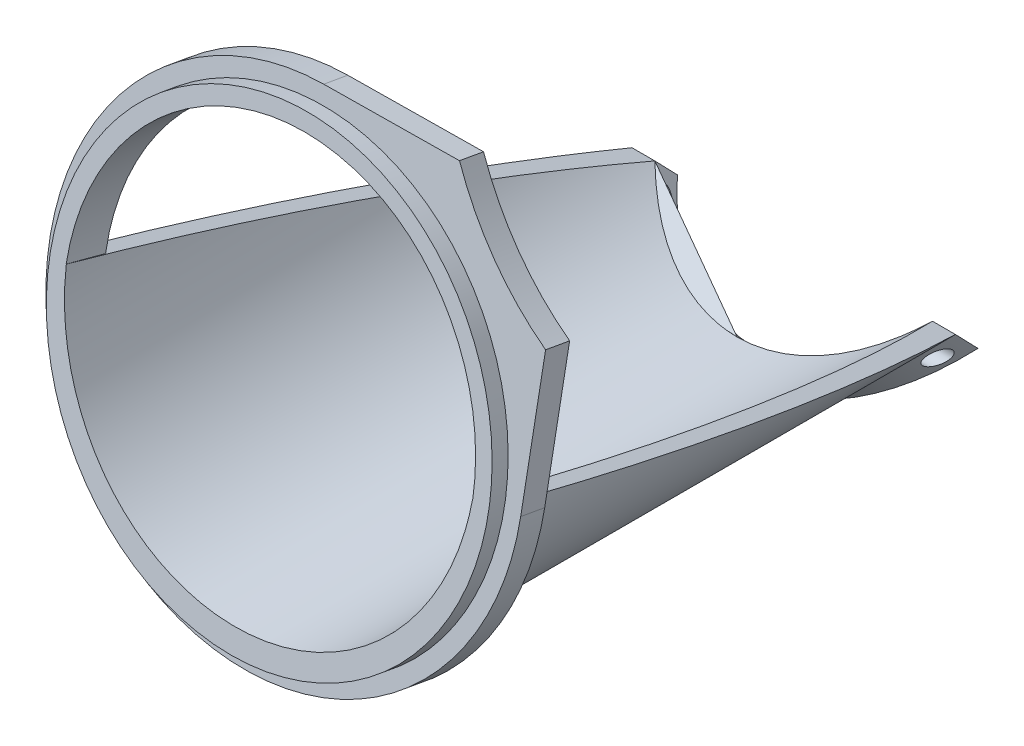
SolidWorks part; units mm, degrees
ref_plane "Front Plane" through (0, 0, 0) normal (0, 0, 1) x (1, 0, 0)
ref_plane "Top Plane" through (0, 0, 0) normal (0, 1, 0) x (1, 0, 0)
ref_plane "Right Plane" through (0, 0, 0) normal (1, 0, 0) x (0, 0, -1)
ref_plane "Plane1" through (0, 0, 90) normal (0, 0, 1) x (1, 0, 0)
ref_axis "Axis1" through (-88.99, 0, 90) along (1, 0, 0)
ref_plane "Plane2" through (0, 15.3909, 87.2862) normal (0, 0.1736, 0.9848) x (1, 0, 0)
sketch "Sketch1" plane through (0, 0, 0) normal (0, 0, 1) x (1, 0, 0)
  line L1 (25, 27) -> (25, 29)
  line L2 (-26.9258, 29) -> (-25, 29)
  line L5 (-25, 29) -> (-25, 27)
  line L6 (25, 29) -> (26.9258, 29)
  arc A0 (25, 27) -> (-25, 27) centre (0, 27) cw
  arc A1 (26.9258, 29) -> (-26.9258, 29) centre (0, 27) cw
  point P1 (0, 0)
  point P6 (0, 0)
  dimension "D1" = 25
  dimension "D3" = 27
  dimension "D2" = 50
  dimension "D4" = 2
extrude "Main" add sketch "Sketch1" along normal blind 90
sketch "Sketch11" plane through (0, 0, 0) normal (1, 0, 0) x (0, 0, -1)
  line L0 (-84.8865, 29) -> (0, 29)
  line L1 (-84.8865, 29) -> (-85.4155, 26)
  line L3 (0, 3.113) -> (0, 29)
  line L6 (0, 27) -> (0, 2) construction
  line L7 (-85.4155, 26) -> (0, 3.113)
  line L8 (-70.2879, 111.7928) -> (-104.2844, -81.0109) construction
  line L9 (-90, 29) -> (0, 29) construction
  point P4 (-84.4058, 31.7261)
  point P9 (-83.9028, 30.9372)
  point P10 (-85.2023, 27.2089)
  point P13 (-84.8865, 29)
  dimension "D1" = 15
  dimension "D2" = 3
extrude "TopSupport" cut sketch "Sketch11" against normal through all both and the other way through all
sketch "Sketch6" plane through (0, 0, 0) normal (1, 0, 0) x (0, 0, -1)
  line L0 (0, 29) -> (0, 0)
  line L1 (0, 27) -> (0, 2) construction
  line L2 (0, 0) -> (-30, 0)
  line L3 (-30, 0) -> (0, 29)
  dimension "D1" = 30
extrude "Back-Extrusion" cut sketch "Sketch6" against normal through all both and the other way through all
sketch "Sketch7" plane through (0, 14.9914, 14.4917) normal (0, -0.719, -0.695) x (1, 0, 0)
  line L0 (19.881, 9.0071) -> (17.0661, 9.0071)
  line L4 (-17.0661, 9.0071) -> (-19.881, 9.0071)
  arc A0 (17.0661, 9.0071) -> (-17.0661, 9.0071) centre (0, -1.1868) ccw
  ellipse E0 centre (0, -17.36) end of major axis (0, 21.5697) minor radius 27.023 (-19.881, 9.0071) -> (19.881, 9.0071) cw
  ellipse E1 centre (0, -18.7656) end of major axis (-27, -18.7656) minor radius 18.7656 (26.9258, -20.1556) -> (-26.9258, -20.1556) ccw construction
  ellipse E2 centre (0, -17.278) end of major axis (0, -56.1257) minor radius 27 (19.881, 9.0071) -> (-19.881, 9.0071) ccw construction
  ellipse E3 centre (0, -17.278) end of major axis (0, -56.1257) minor radius 27 (19.881, 9.0071) -> (-19.881, 9.0071) ccw construction
  ellipse E4 centre (0, -17.278) end of major axis (0, -53.2481) minor radius 25 (17.0661, 9.0071) -> (-17.0661, 9.0071) ccw construction
  point P2 (0, 0)
  point P3 (0, 0)
  point P5 (-19.2049, 5.4678)
  point P6 (0, -12.8298)
  point P12 (26.9258, -20.1556)
  point P13 (26.2279, -8.0545)
  point P29 (-26.9169, -14.232)
  point P31 (0, 0)
  point P32 (23.2948, -4.4368)
  point P33 (-17.3237, -5.1556)
  point P34 (23.5197, -5.0841)
  point P42 (23.4086, 2.0811)
  point P43 (21.6061, 6.0189)
  point P44 (18.2363, 11.3696)
  point P45 (18.2386, 11.3666)
  point P46 (19.367, 5.3088)
  point P47 (0, -17.1197)
extrude "Back" add sketch "Sketch7" along normal blind 4
sketch "Sketch8" plane through (0, 0, 0) normal (1, 0, 0) x (0, 0, -1)
  line L3 (-18.1876, 5.8553) -> (-20.9677, 8.7313) construction
  line L6 (-25.1509, -0.876) -> (-18.1876, 5.8553) construction
  circle A0 centre (-21.3751, 5.5557) radius 1.25
  point P1 (0, 0)
  point P3 (-26.4628, 2.1319)
  point P5 (-22.9753, 7.7297)
  point P10 (-21.1041, 8.9373)
  dimension "D2" = 1.25
  dimension "D3" = 2.5
  dimension "D4" = 2
extrude "RollingHoleSupport" cut sketch "Sketch8" against normal mid plane 50
sketch "Sketch3" plane through (0, 0.3982, 89.9298) normal (0, 0.1736, 0.9848) x (1, 0, 0)
  circle A0 centre (0, 25.8056) radius 25
  circle A1 centre (0, 25.8056) radius 27
  ellipse E0 centre (0, 26.1854) end of major axis (25, 26.1854) minor radius 24.6202 (-25, 26.1854) -> (25, 26.1854) ccw construction
  dimension "D1" = 50
  dimension "D2" = 54
extrude "CircleFix" add sketch "Sketch3" against normal blind 2
sketch "Sketch5" plane through (0, 15.0436, 85.3166) normal (0, 0.1736, 0.9848) x (-1, 0, 0)
  line L0 (0.297, -39.5801) -> (-16.3582, -39.7507)
  line L1 (-29.169, -26.9398) -> (-28.9985, -10.2847)
  line L2 (-46.669, -57.2507) -> (0, -10.5817) construction
  line L5 (0, -10.5817) -> (76.2194, -10.5817) construction
  circle A0 centre (0, -10.5817) radius 25
  arc A1 (0.297, -39.5801) -> (-28.9985, -10.2847) centre (0, -10.5817) ccw
  arc A2 (-16.3582, -39.7507) -> (-29.169, -26.9398) centre (-46.669, -57.2507) ccw
  circle A3 centre (0, -10.5817) radius 25 construction
  point P4 (-21.9203, -32.502)
  point P10 (62.7241, -35.458)
  point P14 (52.2235, -55.2801)
  dimension "D1" = 29
  dimension "D3" = 35
  dimension "D4" = 30
  dimension "D6" = 50
  dimension "D2" = 135
  dimension "D5" = 66
extrude "TriangleFix" add sketch "Sketch5" against normal blind 3
sketch "Sketch12" plane through (0, 15.3909, 87.2862) normal (0, 0.1736, 0.9848) x (1, 0, 0)
  circle A0 centre (0, 15.3066) radius 52.5335
extrude "Cut-Extrude2" cut sketch "Sketch12" along normal through all
